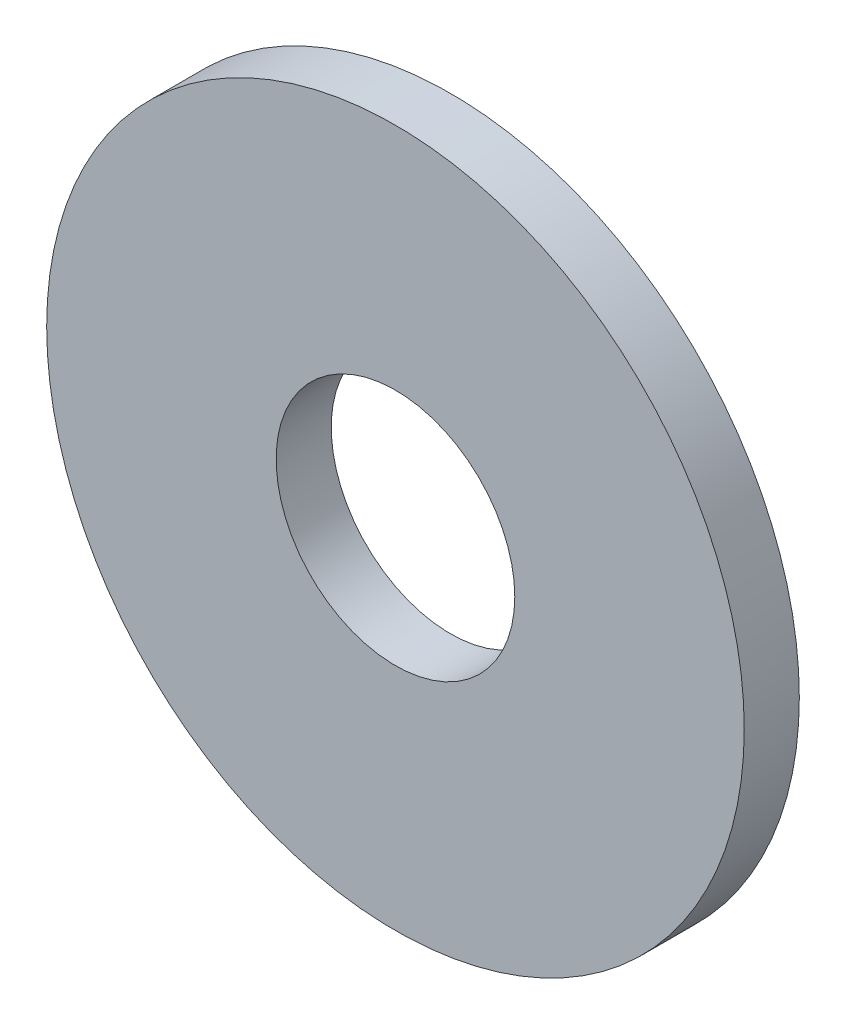
SolidWorks part; units mm, degrees
ref_plane "Top" through (0, 0, 0) normal (0, 0, 1) x (1, 0, 0)
ref_plane "Front" through (0, 0, 0) normal (0, 1, 0) x (1, 0, 0)
ref_plane "Right" through (0, 0, 0) normal (1, 0, 0) x (0, 0, -1)
sketch "Top Sketch" plane through (0, 0, 0) normal (0, 0, 1) x (1, 0, 0)
  circle A0 centre (0, 0) radius 0.65
  circle A1 centre (0, 0) radius 1.9
  dimension "Inside Diameter" = 1.3
  dimension "Outside Diameter" = 3.8
extrude "Extrude Thickness" add sketch "Top Sketch" along normal blind 0.3
equation "\"M2 Close Fit Hole\"= 2.2"
equation "\"M2.5 Close Fit Hole\"= 2.7"
equation "\"M3 Close Fit Hole\"= 3.2"
equation "\"M4 Close Fit Hole\"= 4.3"
equation "\"M5 Close Fit Hole\"= 5.3"
equation "\"M6 Close Fit Hole\"= 6.3"
equation "\"M7 Close Fit Hole\"= 7.4"
equation "\"M8 Close Fit Hole\"= 8.4"
equation "\"M2 Tap Hole 75%\"= 1.6"
equation "\"M3 Tap Hole 75%\"= 2.5"
equation "\"M4 Tap Hole 75%\"= 3.3"
equation "\"M5 Tap Hole 75%\"= 4.2"
equation "\"M6 Tap Hole 75%\"= 5"
equation "\"M7 Tap Hole 75%\"= 6"
equation "\"M8 Tap Hole 75%\"= 6.8"
